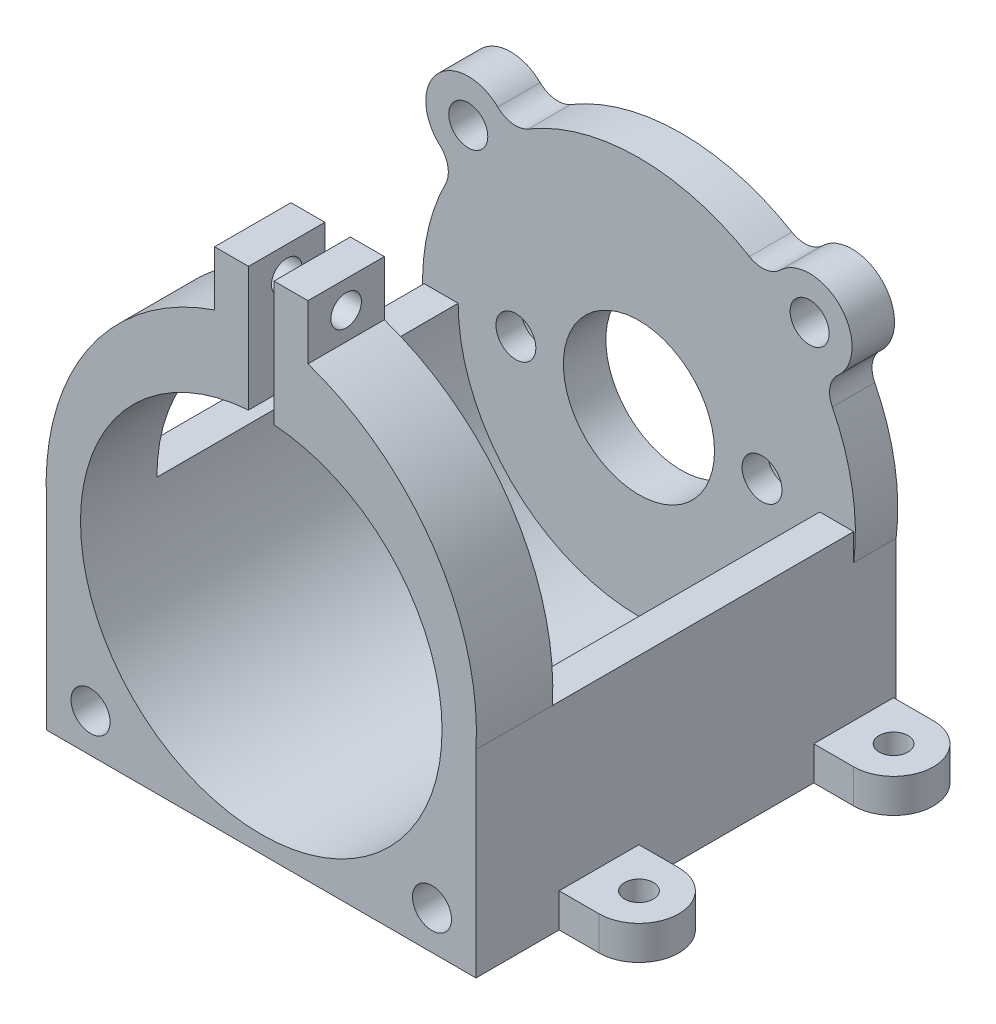
SolidWorks part; units mm, degrees
ref_plane "Спереди" through (0, 0, 0) normal (0, 0, 1) x (1, 0, 0)
ref_plane "Сверху" through (0, 0, 0) normal (0, 1, 0) x (1, 0, 0)
ref_plane "Справа" through (0, 0, 0) normal (1, 0, 0) x (0, 0, -1)
sketch "Эскиз1" plane through (0, 0, 0) normal (0, 0, 1) x (1, 0, 0)
  line L0 (0, 0) -> (-14.5, 0) construction
  line L1 (0, 0) -> (14.5, 0) construction
  line L2 (0, 0) -> (0, 14.5) construction
  line L3 (0, 0) -> (0, -14.5) construction
  circle A1 centre (-14.5, 0) radius 2.35
  circle A2 centre (14.5, 0) radius 2.35
  circle A3 centre (0, 0) radius 8.9
  circle A4 centre (0, 14.5) radius 1.75 construction
  circle A5 centre (0, -14.5) radius 1.75 construction
  arc A70 (-13.0191, -21.9261) -> (-16.6363, -22.3491) centre (-14.5508, -24.5056) ccw
  arc A71 (-13.0191, -21.9261) -> (13.0191, -21.9261) centre (0, 0) ccw
  arc A72 (16.6363, -22.3491) -> (13.0191, -21.9261) centre (14.5508, -24.5056) ccw
  arc A73 (16.6363, -22.3491) -> (23.4552, -15.0368) centre (20.1122, -18.755) ccw
  arc A74 (22.7808, -11.4579) -> (23.4552, -15.0368) centre (25.4609, -12.8059) ccw
  arc A75 (22.7808, -11.4579) -> (22.7808, 11.4579) centre (0, 0) ccw
  arc A76 (23.4552, 15.0368) -> (22.7808, 11.4579) centre (25.4609, 12.8059) ccw
  arc A77 (23.4552, 15.0368) -> (16.6363, 22.3491) centre (20.1122, 18.755) ccw
  arc A78 (13.0191, 21.9261) -> (16.6363, 22.3491) centre (14.5508, 24.5056) ccw
  arc A79 (13.0191, 21.9261) -> (-13.0191, 21.9261) centre (0, 0) ccw
  arc A80 (-16.6363, 22.3491) -> (-13.0191, 21.9261) centre (-14.5508, 24.5056) ccw
  arc A81 (-16.6363, 22.3491) -> (-23.4552, 15.0368) centre (-20.1122, 18.755) ccw
  arc A82 (-22.7808, 11.4579) -> (-23.4552, 15.0368) centre (-25.4609, 12.8059) ccw
  arc A83 (-22.7808, 11.4579) -> (-22.7808, -11.4579) centre (0, 0) ccw
  arc A84 (-23.4552, -15.0368) -> (-22.7808, -11.4579) centre (-25.4609, -12.8059) ccw
  arc A85 (-23.4552, -15.0368) -> (-16.6363, -22.3491) centre (-20.1122, -18.755) ccw
  dimension "D2" = 4.7
  dimension "D3" = 14.5
  dimension "D4" = 17.8
  dimension "D5" = 3.5
  dimension "D1" = 14.5
extrude "Бобышка-Вытянуть1" add sketch "Эскиз1" along normal blind 5
sketch "Эскиз2" plane through (0, 0, 5) normal (0, 0, 1) x (1, 0, 0)
  line L0 (-25.3, 0) -> (-21.3, 0)
  line L1 (21.3, 0) -> (25.3, 0)
  line L2 (0, -28.25) -> (0, -23.25) construction
  line L3 (0, -23.25) -> (16.0468, -23.25) construction
  line L4 (35.3, -23.25) -> (50, -23.25)
  line L5 (-35.3, -23.25) -> (-50, -23.25)
  line L6 (-25.3, 0) -> (-25.3, -13.25)
  line L7 (25.3, 0) -> (25.3, -13.25)
  line L8 (-50, -23.25) -> (-50, -28.25)
  line L9 (-50, -28.25) -> (50, -28.25)
  line L10 (50, -28.25) -> (50, -23.25)
  arc A0 (-21.3, 0) -> (21.3, 0) centre (0, 0) ccw
  arc A2 (35.3, -23.25) -> (25.3, -13.25) centre (35.3, -13.25) cw
  arc A3 (-25.3, -13.25) -> (-35.3, -23.25) centre (-35.3, -13.25) cw
  dimension "D1" = 10
  dimension "D6" = 21.3
  dimension "D2" = 5
  dimension "D3" = 100
  dimension "D4" = 5
  dimension "D5" = 4
extrude "Бобышка-Вытянуть2" add sketch "Эскиз2" along normal blind 44.5 and the other way blind 5
sketch "Эскиз4" plane through (0, 0, 49.5) normal (0, 0, 1) x (1, 0, 0)
  line L0 (0, 0) -> (0, 30) construction
  line L1 (21.3, 0) -> (25.3, 0)
  line L2 (-25.3, 0) -> (-21.3, 0)
  line L3 (0, 30) -> (-1.5, 30) construction
  line L4 (0, 30) -> (1.5, 30) construction
  line L5 (-1.5, 29.9162) -> (-1.5, 21.2471)
  line L6 (1.5, 29.9162) -> (1.5, 21.2471)
  line L7 (-1.5, 29.9162) -> (-1.5, 35.9162)
  line L8 (-1.5, 35.9162) -> (-5.5, 35.9162)
  line L9 (-5.5, 35.9162) -> (-5.5, 29.4654)
  line L10 (1.5, 29.9162) -> (1.5, 35.9162)
  line L11 (1.5, 35.9162) -> (5.5, 35.9162)
  line L12 (5.5, 35.9162) -> (5.5, 29.4654)
  arc A0 (21.3, 0) -> (1.5, 21.2471) centre (0, 0) ccw
  arc A1 (-5.5, 29.4654) -> (-25.3, 0) centre (3.9362, 1.7393) ccw
  arc A2 (5.5, 29.4654) -> (25.3, 0) centre (-3.9362, 1.7393) cw
  arc A3 (-1.5, 21.2471) -> (-21.3, 0) centre (0, 0) ccw
  dimension "D1" = 30
  dimension "D2" = 1.5
  dimension "D3" = 6
  dimension "D4" = 4
extrude "Бобышка-Вытянуть3" add sketch "Эскиз4" against normal blind 9
sketch "Эскиз5" plane through (-5.5, 0, 0) normal (-1, 0, 0) x (0, 0, 1)
  line L0 (45, 35.9162) -> (45, 29.4654) construction
  line L1 (40.5, 35.9162) -> (49.5, 35.9162) construction
  line L2 (40.5, 29.4654) -> (49.5, 29.4654) construction
  circle A0 centre (45, 32.6908) radius 1.8
  dimension "D1" = 3.6
extrude "Вырез-Вытянуть2" cut sketch "Эскиз5" against normal blind 19
sketch "Эскиз9" plane through (0, -23.25, 0) normal (0, 1, 0) x (1, 0, 0)
  line L0 (25.3, 0) -> (25.3, -49.5)
  line L1 (-25.3, 0) -> (25.3, 0)
  line L2 (-25.3, 0) -> (-25.3, -49.5)
  line L3 (-25.3, -49.5) -> (25.3, -49.5)
  line L5 (-59.8904, -57.7314) -> (58.8188, -57.7314)
  line L6 (-59.8904, -57.7314) -> (-59.8904, 10.3746)
  line L7 (-59.8904, 10.3746) -> (58.8188, 10.3746)
  line L8 (58.8188, -57.7314) -> (58.8188, 10.3746)
  line L9 (25.3, -49.5) -> (35.3, -49.5) construction
extrude "Вырез-Вытянуть5" cut sketch "Эскиз9" against normal blind 10 and the other way blind 10
sketch "Эскиз10" plane through (0, 0, 49.5) normal (0, 0, 1) x (1, 0, 0)
  line L0 (0, -21.3) -> (0, -23.3) construction
  line L1 (-25.3, -28.25) -> (-25.3, -23.3)
  line L2 (-25.3, 0) -> (-25.3, -28.25) construction
  line L3 (-25.3, -23.3) -> (25.3, -23.3)
  line L4 (25.3, -28.25) -> (25.3, 0) construction
  line L5 (25.3, -23.3) -> (25.3, -28.25)
  line L6 (25.3, -28.25) -> (-25.3, -28.25)
  arc A0 (-1.5, 21.2471) -> (1.5, 21.2471) centre (0, 0) ccw construction
  dimension "D1" = 2
extrude "Вырез-Вытянуть6" cut sketch "Эскиз10" against normal through all
sketch "Эскиз11" plane through (0, 0, 0) normal (0, 0, -1) x (-1, 0, 0)
  circle A1 centre (-20.1122, -18.755) radius 2.3
  circle A2 centre (20.1122, -18.755) radius 2.3
  dimension "D1" = 4.6
extrude "Вырез-Вытянуть7" cut sketch "Эскиз11" against normal through all
sketch "Эскиз12" plane through (0, 0, 0) normal (0, 0, -1) x (-1, 0, 0)
  circle A0 centre (-20.1122, 18.755) radius 2.3
  circle A1 centre (20.1122, 18.755) radius 2.3
  dimension "D1" = 4.6
extrude "Вырез-Вытянуть8" cut sketch "Эскиз12" against normal blind 10
sketch "Эскиз13" plane through (0, 0, 0) normal (0, 0, -1) x (-1, 0, 0)
  circle A0 centre (-14.5, 0) radius 4.5
  circle A1 centre (14.5, 0) radius 4.5
  dimension "D1" = 9
extrude "Вырез-Вытянуть9" cut sketch "Эскиз13" against normal blind 2
sketch "Эскиз14" plane through (0, -23.3, 0) normal (0, -1, 0) x (1, 0, 0)
  line L0 (0, 0) -> (0, 35) construction
  line L1 (0, 35) -> (-30, 35) construction
  line L2 (-30, 39.7) -> (-25.3, 39.7)
  line L3 (-25.3, 0) -> (-25.3, 49.5) construction
  line L4 (-30, 30.3) -> (-25.3, 30.3)
  line L5 (-25.3, 39.7) -> (-25.3, 30.3)
  line L6 (25.3, 39.7) -> (25.3, 30.3)
  line L7 (30, 30.3) -> (25.3, 30.3)
  line L8 (30, 39.7) -> (25.3, 39.7)
  line L9 (0, 20) -> (-25.3, 20) construction
  line L10 (30, 0.3) -> (25.3, 0.3)
  line L11 (30, 9.7) -> (25.3, 9.7)
  line L12 (25.3, 0.3) -> (25.3, 9.7)
  line L13 (-25.3, 0.3) -> (-25.3, 9.7)
  line L14 (-30, 9.7) -> (-25.3, 9.7)
  line L15 (-30, 0.3) -> (-25.3, 0.3)
  line L17 (25.3, 0) -> (-25.3, 0) construction
  circle A0 centre (-30, 35) radius 1.7
  arc A1 (-30, 39.7) -> (-30, 30.3) centre (-30, 35) ccw
  arc A2 (30, 39.7) -> (30, 30.3) centre (30, 35) cw
  circle A3 centre (30, 35) radius 1.7
  circle A4 centre (30, 5) radius 1.7
  arc A5 (30, 0.3) -> (30, 9.7) centre (30, 5) ccw
  arc A6 (-30, 0.3) -> (-30, 9.7) centre (-30, 5) cw
  circle A7 centre (-30, 5) radius 1.7
  dimension "D1" = 3.4
  dimension "D2" = 3
  dimension "D3" = 35
  dimension "D4" = 30
  dimension "D5" = 20
extrude "Бобышка-Вытянуть4" add sketch "Эскиз14" against normal blind 4
